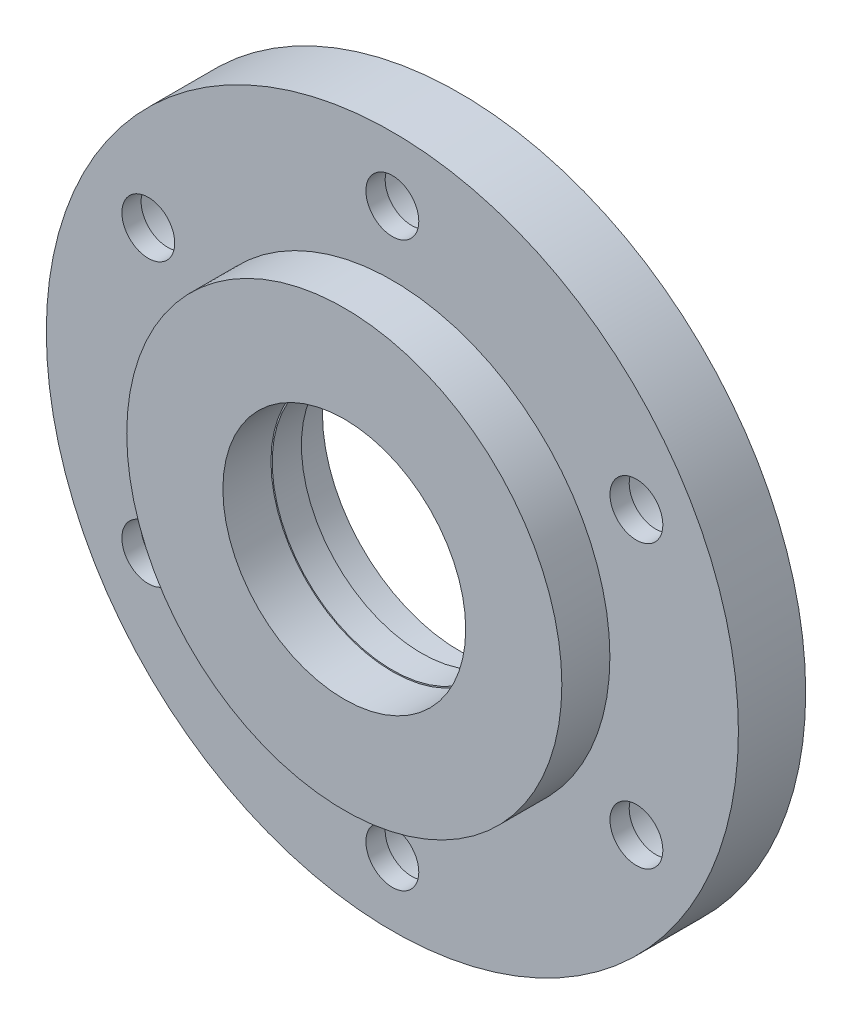
SolidWorks part; units mm, degrees
material "6061-T6 (SS)"
ref_plane "Front Plane" through (0, 0, 0) normal (0, 0, 1) x (1, 0, 0)
ref_plane "Top Plane" through (0, 0, 0) normal (0, 1, 0) x (1, 0, 0)
ref_plane "Right Plane" through (0, 0, 0) normal (1, 0, 0) x (0, 0, -1)
sketch "Sketch Spindle Skeleton" plane through (0, 0, 0) normal (1, 0, 0) x (0, 0, -1)
  line L0 (-116.9, -9.5) -> (-149, -9.5)
  line L5 (-1000, 0) -> (49000, 0)
  line L6 (0, -9.5) -> (0, 9.5)
  line L13 (0, 9.5) -> (-55.3, 9.5)
  line L26 (-55.3, 9.5) -> (-55.3, 14)
  line L27 (-55.3, 14) -> (-116.9, 14)
  line L32 (-116.9, 14) -> (-116.9, 9.5)
  line L34 (-165, 7) -> (-165, -7)
  line L36 (-116.9, -9.5) -> (-116.9, -14)
  line L37 (-116.9, -14) -> (-55.3, -14)
  line L38 (-55.3, -14) -> (-55.3, -9.5)
  line L39 (0, -9.5) -> (-55.3, -9.5)
  line L40 (-20.873, 36) -> (-13.873, 36)
  line L41 (-133.5, 22.6312) -> (-116.9, 22.6312)
  line L42 (-133.5, 22.6312) -> (-133.5, -22.6312)
  line L43 (-133.5, -22.6312) -> (-116.9, -22.6312)
  line L44 (-116.9, 22.6312) -> (-116.9, -22.6312)
  line L45 (-133.5, 22.6312) -> (-116.9, -22.6312) construction
  line L46 (-133.5, -22.6312) -> (-116.9, 22.6312) construction
  line L47 (-38.7, 22.6312) -> (-55.3, 22.6312)
  line L48 (-38.7, 22.6312) -> (-38.7, -22.6312)
  line L49 (-38.7, -22.6312) -> (-55.3, -22.6312)
  line L50 (-55.3, 22.6312) -> (-55.3, -22.6312)
  line L51 (-38.7, 22.6312) -> (-55.3, -22.6312) construction
  line L52 (-38.7, -22.6312) -> (-55.3, 22.6312) construction
  line L59 (-13.873, 36) -> (-13.873, -36)
  line L60 (-13.873, -36) -> (-20.873, -36)
  line L61 (-20.873, -22.6312) -> (-25.873, -22.6312)
  line L62 (-25.873, -22.6312) -> (-25.873, -12.6312)
  line L63 (-25.873, -12.6312) -> (-20.873, -12.6312)
  line L64 (-20.873, -12.6312) -> (-20.873, 12.6312)
  line L65 (-20.873, 12.6312) -> (-25.873, 12.6312)
  line L66 (-25.873, 12.6312) -> (-25.873, 22.6312)
  line L67 (-25.873, 22.6312) -> (-20.873, 22.6312)
  line L68 (-20.873, 22.6312) -> (-20.873, 36)
  line L69 (-20.873, -22.6312) -> (-20.873, -36)
  line L71 (-135.659, 36) -> (-21.873, 36)
  line L72 (-135.659, 36) -> (-135.659, -36)
  line L73 (-135.659, -36) -> (-21.873, -36)
  line L74 (-21.873, 36) -> (-21.873, -36)
  line L75 (-135.659, 36) -> (-21.873, -36) construction
  line L76 (-135.659, -36) -> (-21.873, 36) construction
  line L77 (-149, -9.5) -> (-149, -7)
  line L78 (-149, -7) -> (-165, -7)
  line L79 (-116.9, 9.5) -> (-149, 9.5)
  line L80 (-149, 7) -> (-165, 7)
  line L81 (-149, 9.5) -> (-149, 7)
  line L82 (-132.95, 9.5) -> (-132.95, -9.5) construction
  line L83 (-27.65, 9.5) -> (-27.65, -9.5) construction
  line L96 (-135.659, 36) -> (-142.659, 36)
  line L98 (-135.659, -36) -> (-142.659, -36)
  line L99 (-142.659, 36) -> (-142.659, -36)
  line L110 (-135.659, 36) -> (-135.659, -36)
  point P3 (0, 0)
  point P18 (-125.2, 0)
  point P24 (-47, 0)
  point P29 (-78.766, 0)
  point P48 (-13.873, 29.3156)
  point P70 (-142.659, 29.3156)
revolve "Main Revolve" add sketch "Sketch Spindle Skeleton" angle 360 about L5 region at (0, 22.4882, 17.5776) region at (0, 17.6312, 23.873)
sketch "Sketch Center Cut" plane through (0, 0, 20.873) normal (0, 0, 1) x (1, 0, 0)
  circle A0 centre (0, 0) radius 12.6312 construction
  circle A1 centre (0, 0) radius 12.6312 construction
  circle A2 centre (0, 0) radius 12.5
  dimension "D1" = 25
extrude "Cut Center" cut sketch "Sketch Center Cut" against normal through all
hole_wizard "CBORE for M5 SHCS2" positions "Hole wizard sketch 1" profile "Hole wizard sketch 2" counterbore size "M5" standard "ANSI Metric" end condition through all
sketch "Hole wizard sketch 1" plane through (0, 0, 13.873) normal (0, 0, -1) x (-1, 0, 0)
  point P0 (0, 29.3156)
sketch "Hole wizard sketch 2" plane through (0, 29.3156, 13.873) normal (1, 0, 0) x (0, 1, 0)
  line L0 (0, 0) -> (0, 12)
  line L1 (0, 12) -> (2.75, 12)
  line L3 (2.75, 12) -> (2.75, 5)
  line L4 (2.75, 5) -> (5, 5)
  line L5 (5, 5) -> (5, 0)
  line L7 (5, 0) -> (0, 0)
  line L11 (0, -6.35) -> (0, 107.95) construction
  dimension "Thru Hole Dia." = 5.5
  dimension "Thru Hole Depth" = 12
  dimension "C'Bore Dia." = 10
  dimension "C'Bore Depth" = 5
pattern_circular "CirPattern1" count 6 over 360 about axis through (0, 0, 13.873) along (0, 0, 1) of "CBORE for M5 SHCS2"
sketch "Sketch1" plane through (0, 0, 13.873) normal (0, 0, -1) x (-1, 0, 0)
  circle A0 centre (0, 0) radius 14.2748
  dimension "D1" = 28.5496
extrude "Cut-Extrude1" cut sketch "Sketch1" against normal blind 3.9624
